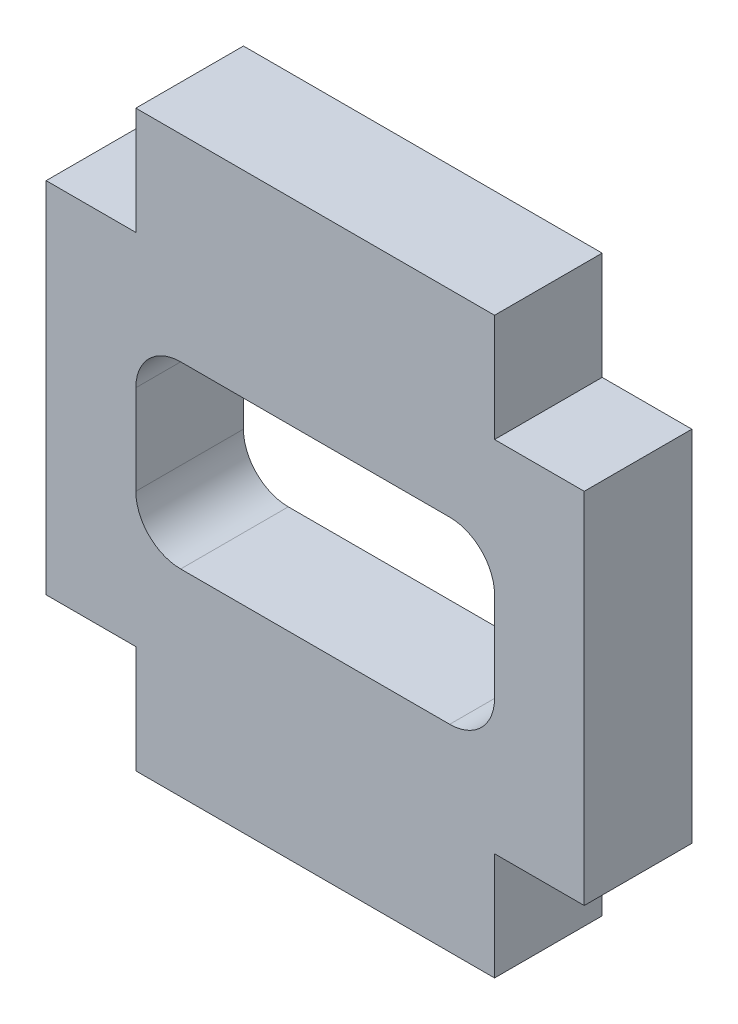
SolidWorks part; units mm, degrees
material "Acrílico (Impacto medio-alto)"
ref_plane "Alzado" through (0, 0, 0) normal (0, 0, 1) x (1, 0, 0)
ref_plane "Planta" through (0, 0, 0) normal (0, 1, 0) x (1, 0, 0)
ref_plane "Vista lateral" through (0, 0, 0) normal (1, 0, 0) x (0, 0, -1)
sketch "Croquis1" plane through (0, 0, 0) normal (0, 0, 1) x (1, 0, 0)
  line L0 (0, 0) -> (-7.6546, 0) construction
  line L1 (7.5, -8) -> (-7.5, -8)
  line L2 (7.5, -8) -> (7.5, 8)
  line L3 (7.5, 8) -> (-7.5, 8)
  line L4 (-7.5, -8) -> (-7.5, 8)
  line L5 (7.5, -8) -> (-7.5, 8) construction
  line L6 (7.5, 8) -> (-7.5, -8) construction
  line L7 (-10, 5) -> (-5, 5)
  line L8 (-10, 5) -> (-10, 11)
  line L9 (-10, 11) -> (-5, 11)
  line L10 (-5, 5) -> (-5, 11)
  line L11 (-10, 5) -> (-5, 11) construction
  line L12 (-10, 11) -> (-5, 5) construction
  line L13 (0, 0) -> (0, 14.1654) construction
  line L14 (10, 11) -> (5, 11)
  line L15 (5, 5) -> (5, 11)
  line L16 (10, 5) -> (5, 5)
  line L17 (10, 5) -> (10, 11)
  line L18 (-10, -11) -> (-5, -11)
  line L19 (-5, -5) -> (-5, -11)
  line L20 (-10, -5) -> (-5, -5)
  line L21 (-10, -5) -> (-10, -11)
  line L22 (10, -5) -> (10, -11)
  line L23 (10, -5) -> (5, -5)
  line L24 (5, -5) -> (5, -11)
  line L25 (10, -11) -> (5, -11)
  line L27 (3.75, -2.5) -> (-3.75, -2.5)
  line L28 (5, -1.25) -> (5, 1.25)
  line L29 (3.75, 2.5) -> (-3.75, 2.5)
  line L30 (-5, -1.25) -> (-5, 1.25)
  line L31 (5, -2.5) -> (-5, 2.5) construction
  line L32 (5, 2.5) -> (-5, -2.5) construction
  arc A0 (-3.75, -2.5) -> (-5, -1.25) centre (-3.75, -1.25) cw
  arc A1 (-3.75, 2.5) -> (-5, 1.25) centre (-3.75, 1.25) ccw
  arc A2 (5, 1.25) -> (3.75, 2.5) centre (3.75, 1.25) ccw
  arc A3 (5, -1.25) -> (3.75, -2.5) centre (3.75, -1.25) cw
  point P0 (0, 0)
  dimension "D7" = 1.25
  dimension "D1" = 16
  dimension "D2" = 15
  dimension "D3" = 6
  dimension "D4" = 5
  dimension "D5" = 5
  dimension "D6" = 10
extrude "Saliente-Extruir1" add sketch "Croquis1" along normal blind 3 contours L24 L23 L2 L16 L15 L3 L10 L7 L4 L20 L19 L1 region at (0, -7.7807, 0)
